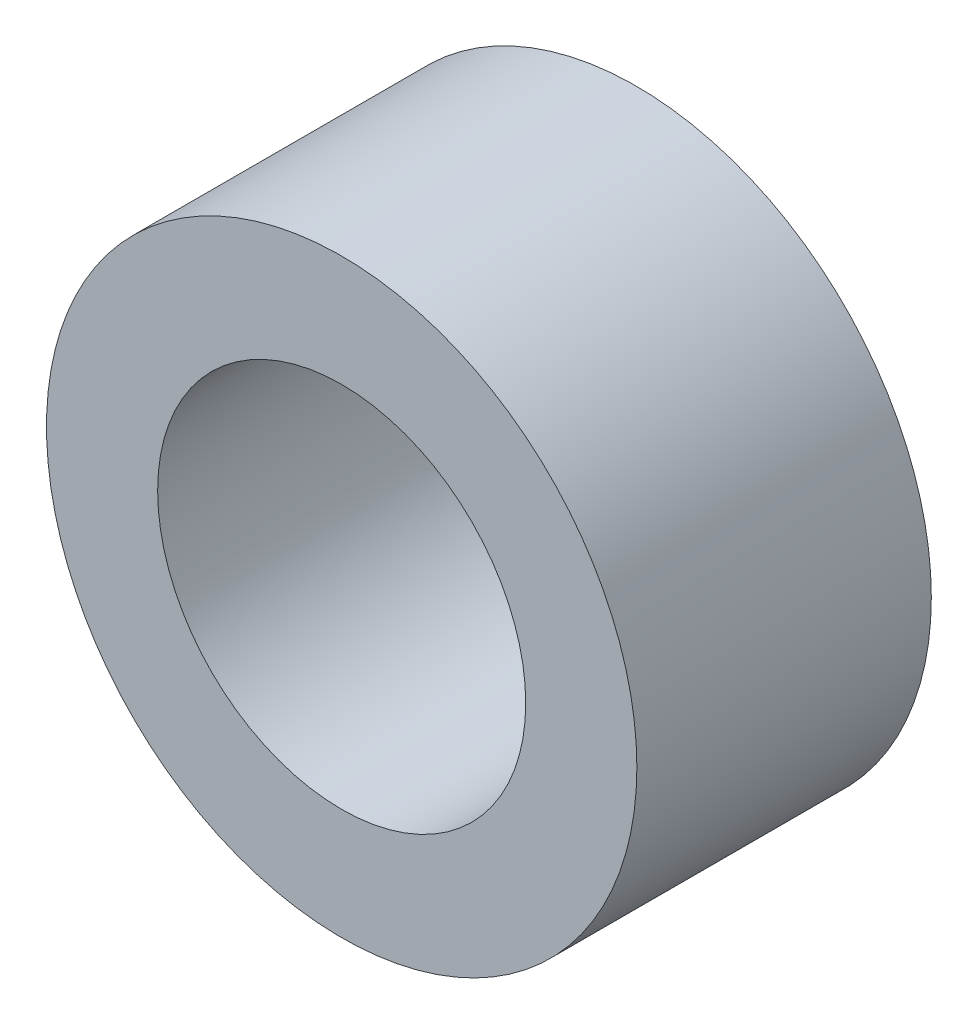
SolidWorks part; units mm, degrees
material "Tin Bearing Bronze"
ref_plane "Front Plane" through (0, 0, 0) normal (0, 0, 1) x (1, 0, 0)
ref_plane "Top Plane" through (0, 0, 0) normal (0, 1, 0) x (1, 0, 0)
ref_plane "Right Plane" through (0, 0, 0) normal (1, 0, 0) x (0, 0, -1)
sketch "Sketch1" plane through (0, 0, 0) normal (0, 0, 1) x (1, 0, 0)
  circle A0 centre (0, 0) radius 4.01
  circle A1 centre (0, 0) radius 2.5
  dimension "D1" = 8.02
  dimension "ID" = 5
extrude "Extrude1" add sketch "Sketch1" along normal mid plane 4
sketch "Sketch2" plane through (0, 0, 0) normal (1, 0, 0) x (0, 0, -1)
  line L0 (-2, -2.5) -> (2, -2.5) construction
  line L3 (2, 2.5) -> (-2, 2.5) construction
  line L5 (-2, -2.5) -> (2, -2.5)
  line L6 (2, 2.5) -> (-2, 2.5)
sketch "Sketch4" plane through (0, 0, 2) normal (0, 0, 1) x (1, 0, 0)
  line L0 (0, 0) -> (-1.7678, 1.7678)
  line L1 (0, -3.3) -> (0, 3.3) construction
  circle A0 centre (0, 0) radius 2.5 construction
  dimension "D1" = 45
ref_axis "Center Axis 1" through (0, 0, -22) along (0, 0, 1)
ref_plane "Contaxt Plane 1" through (0, 0, 2) normal (0, 0, 1) x (1, 0, 0)
ref_plane "Contact Plane 2" through (0, 0, -2) normal (0, 0, -1) x (-1, 0, 0)
